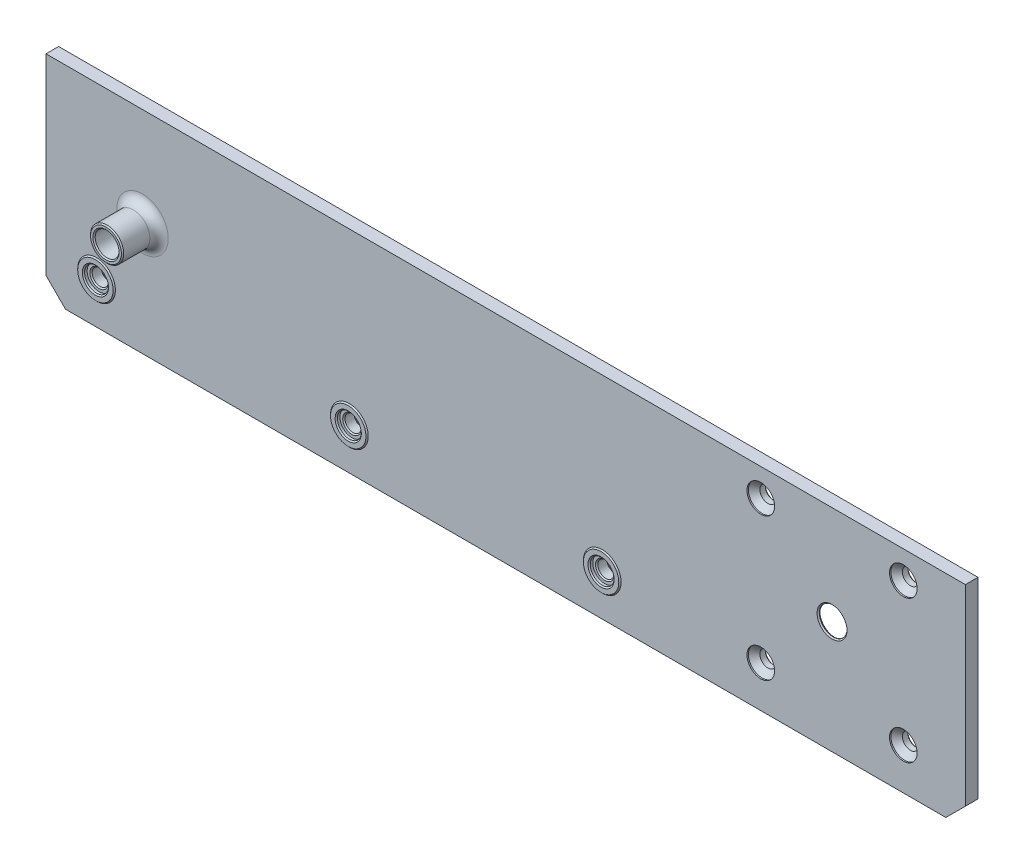
SolidWorks part; units mm, degrees
ref_plane "Front Plane" through (0, 0, 0) normal (0, 0, 1) x (1, 0, 0)
ref_plane "Top Plane" through (0, 0, 0) normal (0, 1, 0) x (1, 0, 0)
ref_plane "Right Plane" through (0, 0, 0) normal (1, 0, 0) x (0, 0, -1)
sketch "Sketch1" plane through (0, 0, 0) normal (0, 0, 1) x (1, 0, 0)
  line L0 (-171, 21.5) -> (29, 21.5)
  line L1 (29, 21.5) -> (29, -20.2574)
  line L2 (29, -20.2574) -> (24.7574, -24.5)
  line L3 (24.7574, -24.5) -> (-166.7574, -24.5)
  line L4 (-166.7574, -24.5) -> (-171, -20.2574)
  line L5 (-171, -20.2574) -> (-171, 21.5)
  line L6 (-14.5858, 21) -> (14.5858, 21) construction
  line L7 (21, 14.5858) -> (21, -14.5858) construction
  line L8 (14.5858, -21) -> (-14.5858, -21) construction
  circle A0 centre (15.5, 15.5) radius 1.75
  circle A1 centre (-15.5, 15.5) radius 1.75
  circle A2 centre (15.5, -15.5) radius 1.75
  circle A3 centre (-15.5, -15.5) radius 1.75
  circle A4 centre (0, 0) radius 3
  dimension "D1" = 3.5
  dimension "D8" = 6
  dimension "D2" = 0.5
  dimension "D3" = 8
  dimension "D4" = 135
  dimension "D5" = 6
  dimension "D6" = 3.5
  dimension "D7" = 200
extrude "Boss-Extrude1" add sketch "Sketch1" along normal blind 3
sketch "Sketch2" plane through (0, 0, 0) normal (0, 0, -1) x (-1, 0, 0)
  circle A2 centre (0, 0) radius 11.45
  circle A3 centre (0, 0) radius 11.45
  dimension "D1" = 0.2
extrude "Cut-Extrude1" cut sketch "Sketch2" against normal blind 2.4
sketch "Sketch3" plane through (0, 0, 3) normal (0, 0, 1) x (1, 0, 0)
  line L0 (15.5, -15.5) -> (-15.5, -15.5) construction
  line L1 (-160, -15.5) -> (-105, -15.5) construction
  line L2 (-105, -15.5) -> (-50, -15.5) construction
  circle A0 centre (-50, -15.5) radius 1.75
  circle A1 centre (-105, -15.5) radius 1.75
  circle A2 centre (-160, -15.5) radius 1.75
  dimension "D2" = 3.5
  dimension "D1" = 50
  dimension "D3" = 55
extrude "Cut-Extrude2" cut sketch "Sketch3" against normal up to next
sketch "Sketch4" plane through (0, 0, 3) normal (0, 0, 1) x (1, 0, 0)
  circle A0 centre (-50, -15.5) radius 2.6
  circle A1 centre (-105, -15.5) radius 2.6
  circle A2 centre (-160, -15.5) radius 2.6
  dimension "D1" = 5.2
extrude "Cut-Extrude3" cut sketch "Sketch4" against normal blind 0.55
sketch "Sketch5" plane through (0, 0, 3) normal (0, 0, 1) x (1, 0, 0)
  circle A0 centre (-150, 0) radius 1.75
  point P2 (0, 0)
  dimension "D1" = 3.5
  dimension "D2" = 150
extrude "Cut-Extrude4" cut sketch "Sketch5" against normal up to next
sketch "Sketch10" plane through (0, 0, 3) normal (0, 0, 1) x (1, 0, 0)
  circle A0 centre (-150, 0) radius 2.6
  dimension "D1" = 5.2
extrude "Cut-Extrude5" cut sketch "Sketch10" against normal blind 1
sketch "Sketch6" plane through (0, 0, 3) normal (0, 0, 1) x (1, 0, 0)
  circle A2 centre (-150, 0) radius 3.6
  circle A3 centre (-150, 0) radius 2.6 construction
  circle A4 centre (-150, 0) radius 2.6
  point P4 (-150, -2.6)
  point P5 (-150, -3.6)
  dimension "D1" = 1
extrude "Boss-Extrude2" add sketch "Sketch6" along normal blind 7.95
sketch "Sketch7" plane through (0, 0, 3) normal (0, 0, 1) x (1, 0, 0)
  circle A0 centre (-50, -15.5) radius 2.6 construction
  circle A1 centre (-105, -15.5) radius 2.6 construction
  circle A2 centre (-50, -15.5) radius 2.6
  circle A3 centre (-105, -15.5) radius 2.6
  circle A4 centre (-50, -15.5) radius 3.6
  circle A5 centre (-105, -15.5) radius 3.6
  circle A6 centre (-160, -15.5) radius 2.6 construction
  circle A7 centre (-160, -15.5) radius 2.6
  circle A8 centre (-160, -15.5) radius 3.6
  point P8 (-50, -18.1)
  point P9 (-50, -19.1)
  dimension "D1" = 1
extrude "Boss-Extrude3" add sketch "Sketch7" along normal mid plane 0.5
hole_wizard "CSK for M3 Flat Head Machine Screw1" positions "Sketch8" profile "Sketch9" countersink size "M3" standard "ANSI Metric" end condition through all
sketch "Sketch8" plane through (0, 0, 3) normal (0, 0, 1) x (1, 0, 0)
  point P0 (-15.5, 15.5)
  point P3 (15.5, 15.5)
  point P6 (15.5, -15.5)
  point P9 (-15.5, -15.5)
sketch "Sketch9" plane through (-15.5, 15.5, 3) normal (1, 0, 0) x (0, -1, 0)
  line L0 (0, 0) -> (0, 3)
  line L1 (0, 3) -> (1.75, 3)
  line L2 (1.75, 3) -> (1.75, 1.55)
  line L3 (1.75, 1.55) -> (3, 0.3)
  line L4 (3, 0.3) -> (3, 0)
  line L6 (3, 0) -> (0, 0)
  line L7 (-1.75, 1.55) -> (-3, 0.3) construction
  line L11 (0, -6.35) -> (0, 107.95) construction
  dimension "Thru Hole Dia." = 3.5
  dimension "Thru Hole Depth" = 3
  dimension "C'Sink Dia." = 6
  dimension "C'Sink Angle" = 90
  dimension "Head Clearance" = 0.3
fillet "Fillet1" radius 2 1 edges at (-146.4, 0, 3)
chamfer "Chamfer1" distance 0.5 angle 45 3 edges at (-53.6, -15.5, 3) (-108.6, -15.5, 3) (-163.6, -15.5, 3)
chamfer "Chamfer2" distance 0.25 angle 45 26 edges at (-11.45, 0, 2.4) (-3, 0, 2.4) (-51.75, -15.5, 0) (-106.75, -15.5, 0) (-11.45, 0, 0) (-13.75, -15.5, 0) (-13.75, 15.5, 0) (-71, 21.5, 0) (-171, 0.6213, 0) (-168.8787, -22.3787, 0) (-71, -24.5, 0) (26.8787, -22.3787, 0) (29, 0.6213, 0) (17.25, 15.5, 0) (17.25, -15.5, 0) (-146.4, 0, 10.95) (3, 0, 3) (-48.25, -15.5, 2.45) (-103.25, -15.5, 2.45) (-47.4, -15.5, 3.25) (-102.4, -15.5, 3.25) (-151.75, 0, 0) (-161.75, -15.5, 0) (-158.25, -15.5, 2.45) (-157.4, -15.5, 3.25) (-147.4, 0, 10.95)
